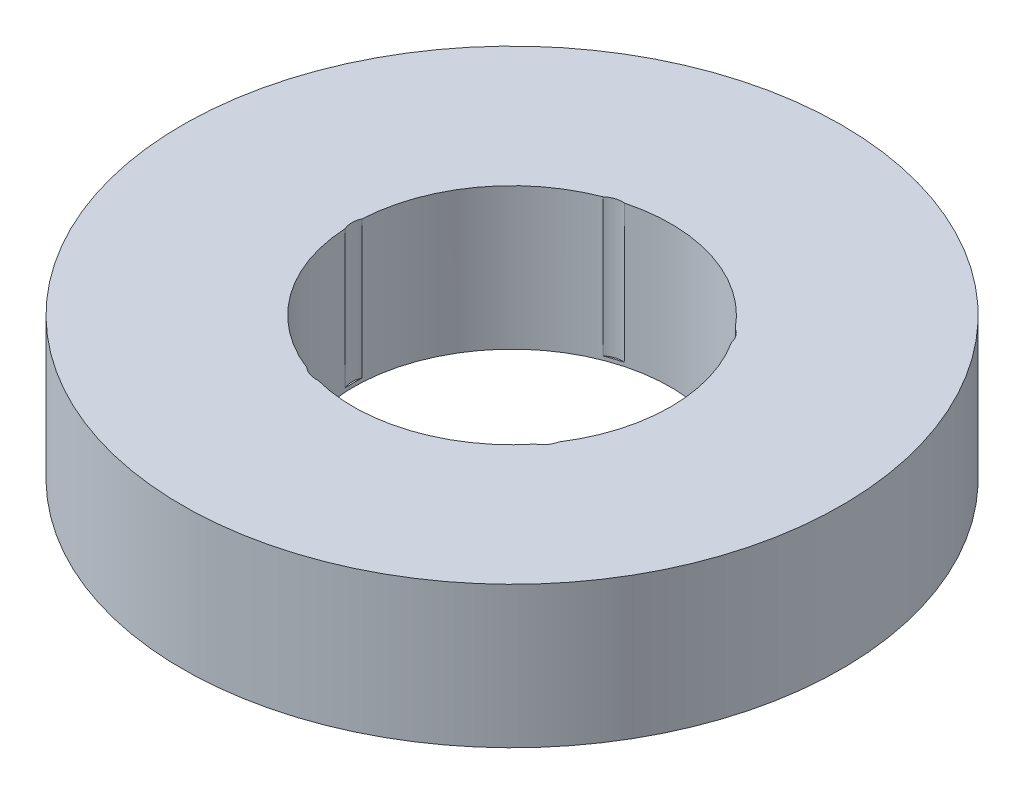
SolidWorks part; units mm, degrees
ref_plane "Front Plane" through (0, 0, 0) normal (0, 0, 1) x (1, 0, 0)
ref_plane "Top Plane" through (0, 0, 0) normal (0, 1, 0) x (1, 0, 0)
ref_plane "Right Plane" through (0, 0, 0) normal (1, 0, 0) x (0, 0, -1)
sketch "Sketch1" plane through (0, 0, 0) normal (0, 1, 0) x (1, 0, 0)
  circle A0 centre (0, 0) radius 67.5
  dimension "FLANGE_OD" = 135
extrude "Boss-Extrude1" add sketch "Sketch1" along normal blind 29
sketch "Sketch2" plane through (0, 0, 0) normal (0, 1, 0) x (1, 0, 0)
  circle A0 centre (0, 0) radius 32.5
  dimension "BORE_D" = 65
extrude "Cut-Extrude1" cut sketch "Sketch2" along normal through all
sketch "Sketch3" plane through (0, 29, 0) normal (0, 1, 0) x (1, 0, 0)
  circle A0 centre (0, 0) radius 28.4332 construction
  circle A1 centre (-28.4332, 0) radius 4.3864
  dimension "BOLT_D" = 8.7728
  dimension "BOLT_PCD" = 56.8663
extrude "Cut-Extrude2" cut sketch "Sketch3" against normal blind 28.2362
pattern_circular "CirPattern1" count 5 over 360 about axis through (0, 0, 0) along (0, 1, 0) of "Cut-Extrude2"
